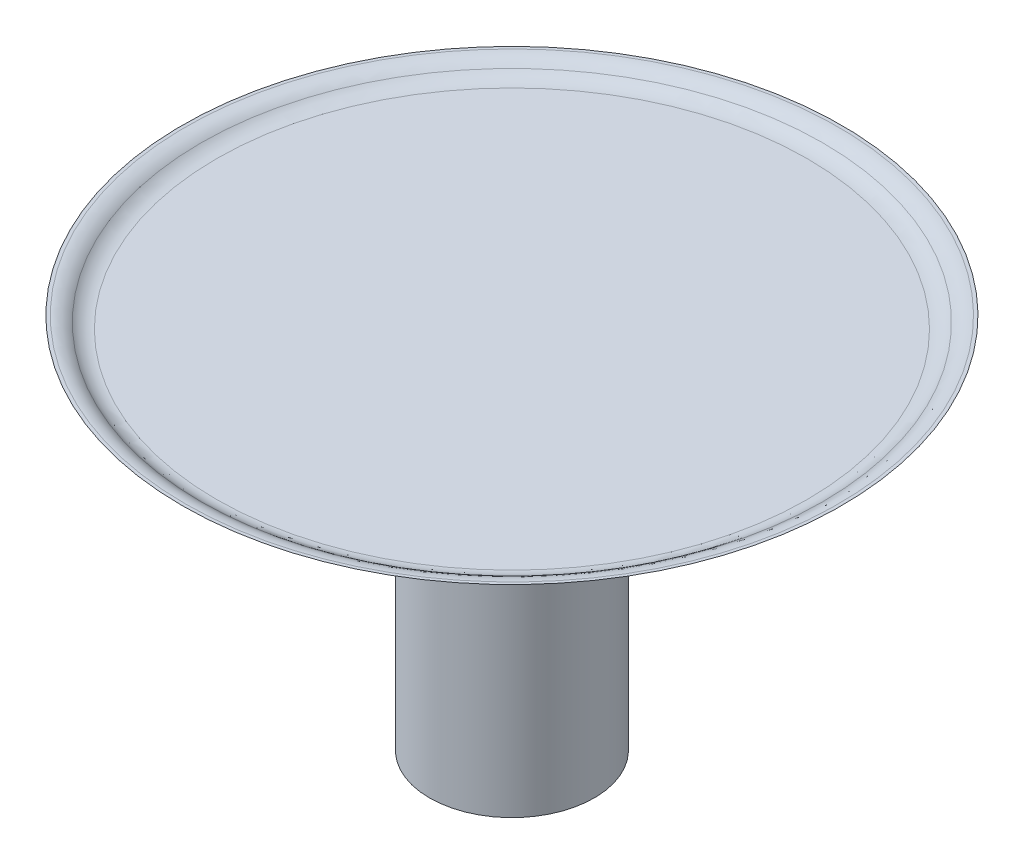
SolidWorks part; units mm, degrees
ref_plane "Front Plane" through (0, 0, 0) normal (0, 0, 1) x (1, 0, 0)
ref_plane "Top Plane" through (0, 0, 0) normal (0, 1, 0) x (1, 0, 0)
ref_plane "Right Plane" through (0, 0, 0) normal (1, 0, 0) x (0, 0, -1)
sketch "Sketch1" plane through (0, 0, 0) normal (0, 1, 0) x (1, 0, 0)
  circle A0 centre (0, 0) radius 3.5
  dimension "D1" = 7
extrude "Boss-Extrude1" add sketch "Sketch1" along normal blind 10
sketch "Sketch2" plane through (0, 10, 0) normal (0, 1, 0) x (1, 0, 0)
  circle A0 centre (0, 0) radius 2.5
  dimension "D1" = 5
extrude "Boss-Extrude2" add sketch "Sketch2" along normal blind 2
sketch "Sketch3" plane through (0, 12, 0) normal (0, 1, 0) x (1, 0, 0)
  circle A0 centre (0, 0) radius 3.5
  dimension "D1" = 7
extrude "Boss-Extrude3" add sketch "Sketch3" along normal blind 2
sketch "Sketch4" plane through (0, 14, 0) normal (0, 1, 0) x (1, 0, 0)
  circle A0 centre (0, 0) radius 14
  dimension "D1" = 28
extrude "Boss-Extrude4" add sketch "Sketch4" along normal blind 2
fillet "Fillet1" radius 10 1 edges at (0, 14, 14)
sketch "Sketch5" plane through (0, 16, 0) normal (0, 1, 0) x (1, 0, 0)
  circle A0 centre (0, 0) radius 13
  dimension "D1" = 26
extrude "Cut-Extrude1" cut sketch "Sketch5" against normal blind 0.5
fillet "Fillet2" radius 1 1 edges at (0, 16, 13)
fillet "Fillet3" radius 1 1 edges at (0, 15.5, 13)
